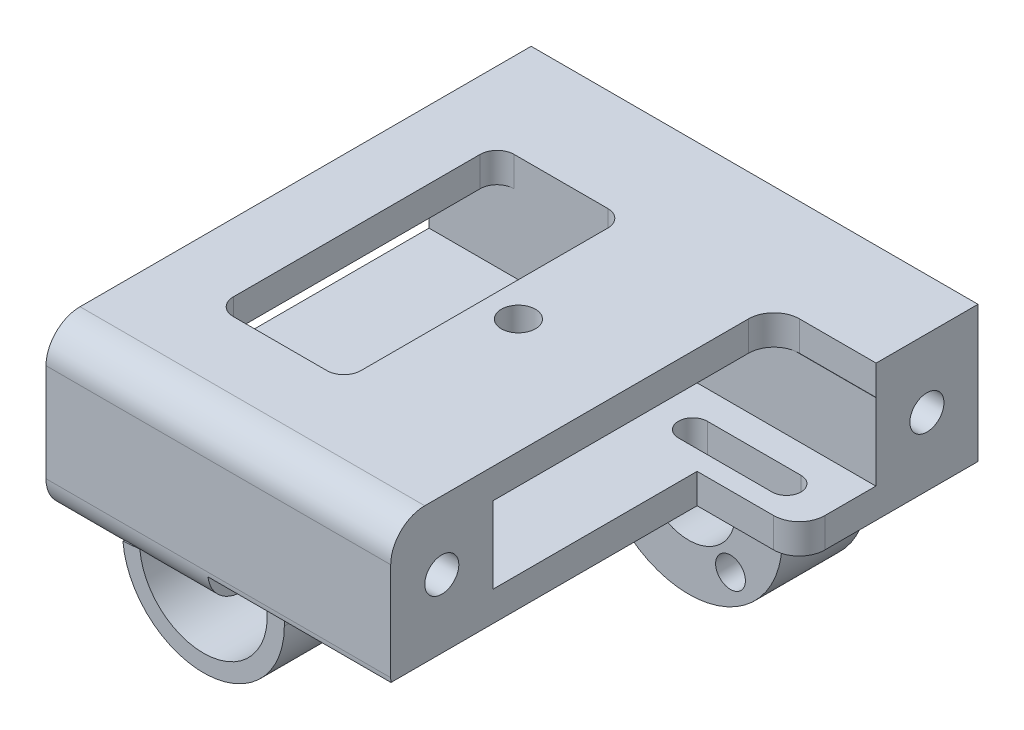
SolidWorks part; units mm, degrees
ref_plane "Front Plane" through (0, 0, 0) normal (0, 0, 1) x (1, 0, 0)
ref_plane "Top Plane" through (0, 0, 0) normal (0, 1, 0) x (1, 0, 0)
ref_plane "Right Plane" through (0, 0, 0) normal (1, 0, 0) x (0, 0, -1)
sketch "Sketch1" plane through (0, 0, 0) normal (0, 0, 1) x (1, 0, 0)
  line L0 (0, 0) -> (0, -35)
  line L1 (0, -35) -> (19, -35)
  line L2 (19, -35) -> (19, -16)
  line L3 (19, -16) -> (52.5, -16)
  line L4 (52.5, -16) -> (52.5, 0)
  line L5 (52.5, 0) -> (0, 0)
  line L6 (0, 0) -> (0.6966, -0.1385)
  dimension "D1" = 35
  dimension "D2" = 19
  dimension "D3" = 52.5
  dimension "D4" = 16
extrude "Boss-Extrude1" add sketch "Sketch1" along normal blind 57 contours L4 L5 L0 L1 L2 L3 region at (21.2152, -13.2602, 0)
ref_plane "Plane1" through (0, 0, 50) normal (0, 0, 1) x (1, 0, 0)
sketch "Sketch3" plane through (0, 0, 0) normal (-1, 0, 0) x (0, 0, 1)
  line L0 (57, 0) -> (0, 0) construction
  line L1 (12, -3.5) -> (45, -3.5)
  line L2 (12, -3.5) -> (12, -12.5)
  line L3 (12, -12.5) -> (45, -12.5)
  line L4 (45, -3.5) -> (45, -12.5)
  line L5 (57, -35) -> (48, -35)
  line L6 (57, -35) -> (57, -19.5)
  line L7 (57, -19.5) -> (48, -19.5)
  line L8 (48, -35) -> (48, -19.5)
  line L9 (0, 0) -> (0, -35) construction
  line L14 (57, -35) -> (0, -35) construction
  dimension "D1" = 9
  dimension "D2" = 33
  dimension "D3" = 3.5
  dimension "D4" = 12
  dimension "D5" = 15.5
  dimension "D6" = 9
extrude "Cut-Extrude2" cut sketch "Sketch3" against normal through all
fillet "Fillet1" radius 4 2 edges at (26.25, 0, 57) (9.5, -19.5, 57)
sketch "Sketch4" plane through (0, 0, 0) normal (0, 0, -1) x (-1, 0, 0)
  line L0 (-9.5, -25.5) -> (-9.5, -35) construction
  line L1 (0, -35) -> (-19, -35) construction
  line L2 (-2.0103, -25.1075) -> (-0.013, -25.0028)
  line L3 (0, -35) -> (-19, -35)
  line L4 (0, -35) -> (0, -16)
  line L5 (0, -16) -> (-19, -16)
  line L6 (-19, -35) -> (-19, -16)
  line L7 (-2.0285, -26.1537) -> (-0.0362, -26.328)
  line L8 (-2.0285, -26.1537) -> (-9.5, -25.5) construction
  line L9 (-0.013, -25.0028) -> (0, -25.0021)
  circle A0 centre (-9.5, -25.5) radius 7.5
  circle A1 centre (-9.5, -25.5) radius 9.5
  line M8 (-19, -35) -> (0, -35)
  line M9 (0, -35) -> (0, 0)
  dimension "D1" = 15
  dimension "D2" = 19
  dimension "D3" = 8
  dimension "D4" = 85
extrude "Cut-Extrude3" cut sketch "Sketch4" against normal through all contours A0 | A1 L6 M8 | L7 A1 L2 A0 | A1 L3 M9 | A1 L4 L9 region at (0.969, -25.6489, 0) region at (9.5, -25.5, 0) region at (0.0039, -25.1268, 0) region at (2.122, -32.878, 0) region at (16.878, -32.878, 0)
sketch "Sketch5" plane through (0, -16, 0) normal (0, -1, 0) x (1, 0, 0)
  line L0 (28, 28.5) -> (32, 28.5) construction
  line L1 (22, 45) -> (26, 45) construction
  line L2 (20, 43) -> (20, 14) construction
  line L3 (22, 12) -> (26, 12) construction
  line L4 (28, 43) -> (28, 14) construction
  line L5 (36, 17) -> (47, 17) construction
  line L6 (36, 18.7) -> (47, 18.7)
  line L7 (36, 15.3) -> (47, 15.3)
  line L8 (19, 56.9686) -> (19, 0) construction
  line L10 (19, 0) -> (52.5, 0) construction
  line L11 (52.5, 0) -> (52.5, 18) construction
  line L12 (52.5, 56.9686) -> (52.5, 0) construction
  line L13 (0, 57) -> (52.5, 57) construction
  line L14 (49.5, 18) -> (49.5, 21) construction
  line L15 (49.5, 21) -> (40.5, 21)
  line L16 (40.5, 21) -> (40.5, 57)
  line L18 (40.5, 57) -> (52.5, 57)
  line L19 (52.5, 57) -> (52.5, 18)
  arc A0 (20, 14) -> (22, 12) centre (22, 14) ccw construction
  arc A1 (26, 12) -> (28, 14) centre (26, 14) ccw construction
  arc A2 (28, 43) -> (26, 45) centre (26, 43) ccw construction
  arc A3 (22, 45) -> (20, 43) centre (22, 43) ccw construction
  circle A4 centre (32, 28.5) radius 2 construction
  arc A5 (36, 18.7) -> (36, 15.3) centre (36, 17) ccw
  arc A6 (47, 15.3) -> (47, 18.7) centre (47, 17) ccw
  arc A7 (52.5, 18) -> (49.5, 21) centre (49.5, 18) ccw
  point P17 (41.5, 17)
  line M12 (52.5, 0) -> (52.5, 56.9686)
  dimension "D1" = 2
  dimension "D4" = 4
  dimension "D6" = 1.7
  dimension "D9" = 2.3
  dimension "D12" = 6
  dimension "D2" = 8
  dimension "D3" = 33
  dimension "D5" = 4
  dimension "D7" = 11
  dimension "D8" = 1
  dimension "D10" = 12
  dimension "D11" = 18
  dimension "D13" = 9
  dimension "D14" = 4.5
extrude "Cut-Extrude4" cut sketch "Sketch5" against normal up to surface (12.5 mm away) contours A4 | L7 A6 L6 A5 | A7 L16 L15 M12 | L19 L18 L16 | L2 A0 L3 A1 L4 A2 L1 A3 region at (41.5, -16, 17) region at (46.5237, -16, 38.9169) up to face at (26.25, -3.5, 28.5)
sketch "Sketch6" plane through (0, 0, 0) normal (0, 1, 0) x (1, 0, 0)
  line L0 (52.5, 0) -> (0, 0) construction
  line L1 (10, -12) -> (21, -12)
  line L2 (8, -14) -> (8, -43)
  line L3 (10, -45) -> (21, -45)
  line L4 (23, -14) -> (23, -43)
  line L5 (0, -53) -> (0, 0) construction
  line L6 (52.5, -56.9686) -> (40.5, -56.9686) construction
  line L7 (43.5, -11.9686) -> (52.5, -11.9686)
  line L8 (40.5, -14.9686) -> (40.5, -56.9686)
  line L9 (40.5, -56.9686) -> (52.5, -56.9686)
  line L10 (52.5, -11.9686) -> (52.5, -56.9686)
  line L11 (52.5, -53) -> (52.5, 0) construction
  line L12 (27, -28.5) -> (23, -28.5) construction
  arc A0 (10, -45) -> (8, -43) centre (10, -43) cw
  arc A1 (23, -43) -> (21, -45) centre (21, -43) cw
  arc A2 (23, -14) -> (21, -12) centre (21, -14) ccw
  arc A3 (10, -12) -> (8, -14) centre (10, -14) ccw
  arc A4 (43.5, -11.9686) -> (40.5, -14.9686) centre (43.5, -14.9686) ccw
  circle A5 centre (27, -28.5) radius 2 construction
  point P6 (8, -45)
  point P11 (23, -12)
  point P14 (8, -12)
  point P25 (40.5, -11.9686)
  dimension "D3" = 2
  dimension "D8" = 3
  dimension "D9" = 4
  dimension "D10" = 4
  dimension "D1" = 33
  dimension "D2" = 15
  dimension "D4" = 12
  dimension "D5" = 8
  dimension "D6" = 45
  dimension "D7" = 12
extrude "Cut-Extrude5" cut sketch "Sketch6" against normal up to surface (3.5 mm away) up to face at (31, -3.5, 37.9895)
sketch "Sketch9" plane through (0, -3.5, 0) normal (0, -1, 0) x (1, 0, 0)
  line L0 (40.5, 21) -> (40.5, 56.9686) construction
  line L1 (19, 0) -> (52.5, 0) construction
  circle A0 centre (27, 28.5) radius 3.2
  dimension "D1" = 6.4
  dimension "D2" = 13.5
  dimension "D3" = 28.5
ref_plane "Plane3" through (0, -5, 0) normal (0, -1, 0) x (-1, 0, 0)
sketch "Sketch10" plane through (0, -5, 0) normal (0, -1, 0) x (-1, 0, 0)
  circle A0 centre (-27, -28.5) radius 2.8
  dimension "D1" = 5.6
loft "Loft1" add profiles "Sketch9", "Sketch10" connector at (30.0985, -3.5, 27.7003) connector at (29.7453, -5, 27.9494)
ref_plane "Plane4" through (0, -8, 0) normal (0, -1, 0) x (-1, 0, 0)
mirror "Mirror2" about plane through (0, -8, 0) normal (0, -1, 0) of "Loft1"
sketch "Sketch11" plane through (0, -11, 0) normal (0, 1, 0) x (1, 0, 0)
  circle A0 centre (27, -28.5) radius 2 construction
  circle A1 centre (27, -28.5) radius 2
extrude "Cut-Extrude6" cut sketch "Sketch11" against normal through all both and the other way through all
sketch "Sketch13" plane through (52.5, 0, 0) normal (1, 0, 0) x (0, 0, -1)
  line L0 (-51, -8) -> (-6, -8) construction
  line L1 (-6, -8) -> (0, -8) construction
  line L2 (0, -16) -> (0, 0) construction
  line L3 (-51, -8) -> (-57, -8) construction
  line L4 (-57, -4) -> (-57, -15.5) construction
  circle A0 centre (-6, -8) radius 2
  circle A1 centre (-51, -8) radius 2
  dimension "D1" = 45
  dimension "D2" = 4
extrude "Cut-Extrude7" cut sketch "Sketch13" against normal blind 20
sketch "Sketch14" plane through (0, 0, 0) normal (0, 0, -1) x (-1, 0, 0)
  line L0 (-28.5, -25.5) -> (-9.5, -25.5) construction
  line L1 (-28.5, -25.5) -> (-28.5, -14.5) construction
  line L2 (-23.5747, -19.1959) -> (-33.4253, -31.8041) construction
  line L3 (-34.8041, -20.5747) -> (-22.1959, -30.4253) construction
  line L4 (-28.5, -14.5) -> (-17.5, -14.5)
  line L5 (-17.5, -14.5) -> (-17.5, -25.5)
  circle A0 centre (-28.5, -25.5) radius 11
  circle A1 centre (-28.5, -25.5) radius 5.5
  circle A2 centre (-28.5, -25.5) radius 8 construction
  circle A3 centre (-23.5747, -19.1959) radius 1.75
  circle A4 centre (-34.8041, -20.5747) radius 1.75
  circle A5 centre (-33.4253, -31.8041) radius 1.75
  circle A6 centre (-22.1959, -30.4253) radius 1.75
  line M8 (-52.5, -16) -> (-19, -16)
  line M9 (-19, -16) -> (-19, -25.5)
  arc M10 (-19, -25.5) -> (-0.0362, -26.328) centre (-9.5, -25.5) ccw
  dimension "D1" = 19
  dimension "D2" = 22
  dimension "D3" = 11
  dimension "D4" = 38
  dimension "D5" = 3.5
  dimension "D6" = 16
extrude "Boss-Extrude2" add sketch "Sketch14" against normal blind 10 contours A0 A6 A5 A4 A3 A1 M9 M8 M10 | A0 M9 M8 region at (20.2019, -17.2019, 0) region at (20.9309, -17.9309, 0)
